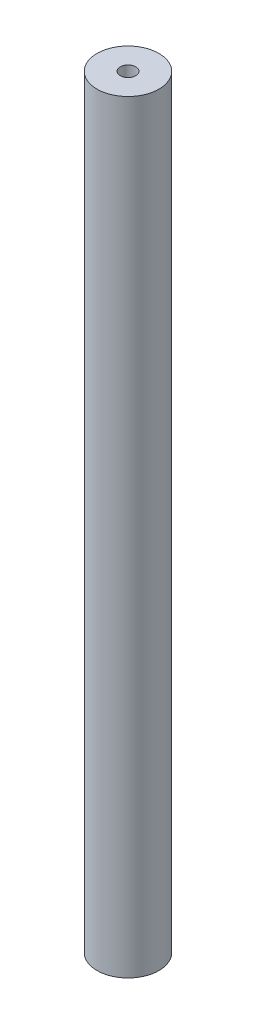
SolidWorks part; units mm, degrees
ref_plane "Front Plane" through (0, 0, 0) normal (0, 0, 1) x (1, 0, 0)
ref_plane "Top Plane" through (0, 0, 0) normal (0, 1, 0) x (1, 0, 0)
ref_plane "Right Plane" through (0, 0, 0) normal (1, 0, 0) x (0, 0, -1)
sketch "Sketch1" plane through (0, 0, 0) normal (0, 1, 0) x (1, 0, 0)
  circle A0 centre (0, 0) radius 6
extrude "Boss-Extrude1" add sketch "Sketch1" along normal blind 148
sketch "Sketch2" plane through (0, 148, 0) normal (0, 1, 0) x (1, 0, 0)
  circle A0 centre (0, 0) radius 1.5
extrude "Cut-Extrude1" cut sketch "Sketch2" against normal blind 5
sketch "Sketch4" plane through (0, 0, 0) normal (0, 0, 1) x (1, 0, 0)
  line L0 (0, 142.3332) -> (0, 174.0208) construction
pattern_linear "LPattern1" count 2 spacing 143 along (0, -1, 0) of "Cut-Extrude1"
